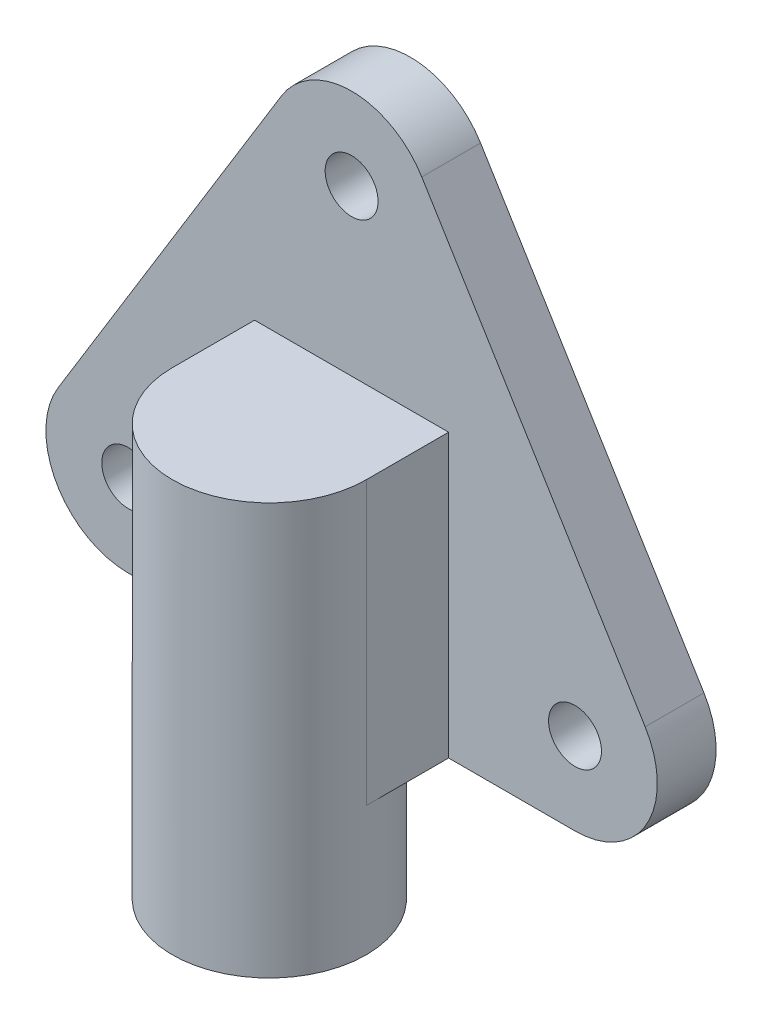
SolidWorks part; units mm, degrees
ref_plane "Front Plane" through (0, 0, 0) normal (0, 0, 1) x (1, 0, 0)
ref_plane "Top Plane" through (0, 0, 0) normal (0, 1, 0) x (1, 0, 0)
ref_plane "Right Plane" through (0, 0, 0) normal (1, 0, 0) x (0, 0, -1)
sketch "Sketch1" plane through (0, 0, 0) normal (0, 0, 1) x (1, 0, 0)
  line L0 (0, 0) -> (0, -63332.1558) construction
  line L1 (0, 0) -> (-63332.1558, 0) construction
  line L2 (-38, -14) -> (38, -14)
  line L3 (-49.9364, 7.3159) -> (-11.9364, 69.3159)
  line L4 (49.9364, 7.3159) -> (11.9364, 69.3159)
  arc A0 (11.9364, 69.3159) -> (-11.9364, 69.3159) centre (0, 62) ccw
  circle A1 centre (0, 62) radius 4.5
  arc A2 (38, -14) -> (49.9364, 7.3159) centre (38, 0) ccw
  circle A3 centre (38, 0) radius 4.5
  arc A4 (-38, -14) -> (-49.9364, 7.3159) centre (-38, 0) cw
  circle A5 centre (-38, 0) radius 4.5
  dimension "D1" = 28
  dimension "D2" = 9
  dimension "D3" = 62
  dimension "D4" = 76
extrude "Boss-Extrude1" add sketch "Sketch1" along normal blind 10
sketch "Sketch2" plane through (0, -14, 0) normal (0, -1, 0) x (1, 0, 0)
  line L0 (0, 0) -> (0, -50000) construction
  line L1 (-38, 10) -> (38, 10) construction
  line L2 (-16.5, 10) -> (16.5, 10)
  line L3 (-16.5, 24) -> (-16.5, 10)
  line L4 (16.5, 24) -> (16.5, 10)
  circle A0 centre (0, 24) radius 16.5
  line M5 (38, 10) -> (-38, 10)
  dimension "D1" = 24
  dimension "D2" = 33
extrude "Boss-Extrude2" add sketch "Sketch2" along normal blind 22 and the other way blind 48 contours L0 A0 M5 | A0 L0 L2 | L0 A0 M5 | L2 L0 A0 region at (0, -14, 24.5376) region at (0, -14, 8.9932)
extrude "Boss-Extrude3" add sketch "Sketch2<3>" against normal blind 48 contours A0 L4 M5 | A0 L3 M5 region at (-14.3074, -14, 13.3143) region at (14.3074, -14, 13.3143)
sketch "Sketch2<3>" plane through (0, -14, 0) normal (0, -1, 0) x (1, 0, 0) same geometry as "Sketch2"
sketch "Sketch5" plane through (0, -36, 0) normal (0, -1, 0) x (1, 0, 0)
  circle A0 centre (0, 24) radius 8
  dimension "D1" = 16
extrude "Cut-Extrude1" cut sketch "Sketch5" against normal blind 54
